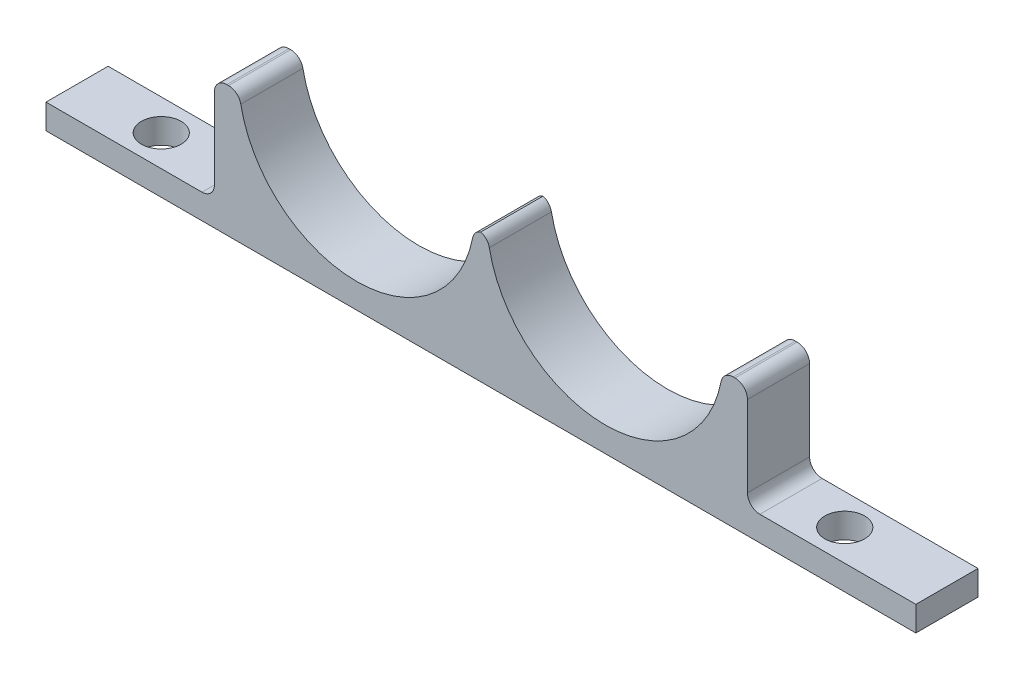
SolidWorks part; units mm, degrees
ref_plane "Plan de face" through (0, 0, 0) normal (0, 0, 1) x (1, 0, 0)
ref_plane "Plan de dessus" through (0, 0, 0) normal (0, 1, 0) x (1, 0, 0)
ref_plane "Plan de droite" through (0, 0, 0) normal (1, 0, 0) x (0, 0, -1)
sketch "Esquisse1" plane through (0, 0, 0) normal (0, 0, 1) x (1, 0, 0)
  line L1 (0, 0) -> (70, 0)
  line L2 (0, 0) -> (0, 2)
  line L3 (13.5528, 10.5) -> (15.5528, 10.5)
  line L4 (70, 0) -> (70, 2)
  line L7 (0, 2) -> (70, 2) construction
  line L8 (13.5528, 10.5) -> (13.5528, 2)
  line L9 (13.5528, 2) -> (0, 2)
  line L10 (35, 10.5) -> (35, 0) construction
  line L11 (56.4472, 2) -> (70, 2)
  line L12 (56.4472, 10.5) -> (56.4472, 2)
  line L13 (34.4472, 10.5) -> (35.5528, 10.5)
  line L15 (54.4472, 10.5) -> (56.4472, 10.5)
  arc A0 (15.5528, 10.5) -> (34.4472, 10.5) centre (25, 11.5) ccw
  arc A1 (35.5528, 10.5) -> (54.4472, 10.5) centre (45, 11.5) ccw
  point P15 (15.5528, 10.5)
  dimension "D2" = 19
  dimension "D4" = 11.5
  dimension "D5" = 20
  dimension "D8" = 1.1056
  dimension "D1" = 70
  dimension "D3" = 8.5
  dimension "D6" = 25
  dimension "D7" = 2
extrude "Boss.-Extru.1" add sketch "Esquisse1" along normal blind 5
sketch "Esquisse2" plane through (0, 2, 0) normal (0, 1, 0) x (1, 0, 0)
  line L0 (0, -2.5) -> (70, -2.5) construction
  line L1 (0, -5) -> (0, 0) construction
  line L2 (70, -5) -> (70, 0) construction
  line L6 (6.7764, 0) -> (6.7764, -5) construction
  line L7 (13.5528, 0) -> (0, 0) construction
  line L8 (13.5528, -5) -> (0, -5) construction
  circle A0 centre (6.7764, -2.5) radius 1.6
  circle A1 centre (61.7764, -2.5) radius 1.6
  point P20 (0, 0)
  dimension "D1" = 3.2
  dimension "D2" = 55
extrude "Enlèv. mat.-Extru.1" cut sketch "Esquisse2" against normal through all
fillet "Congé1" radius 1 1 edges at (13.5528, 2, 2.5)
fillet "Congé2" radius 1 7 edges at (56.4472, 2, 2.5) (54.4472, 10.5, 2.5) (56.4472, 10.5, 2.5) (35.5528, 10.5, 2.5) (34.4472, 10.5, 2.5) (15.5528, 10.5, 2.5) (13.5528, 10.5, 2.5)
